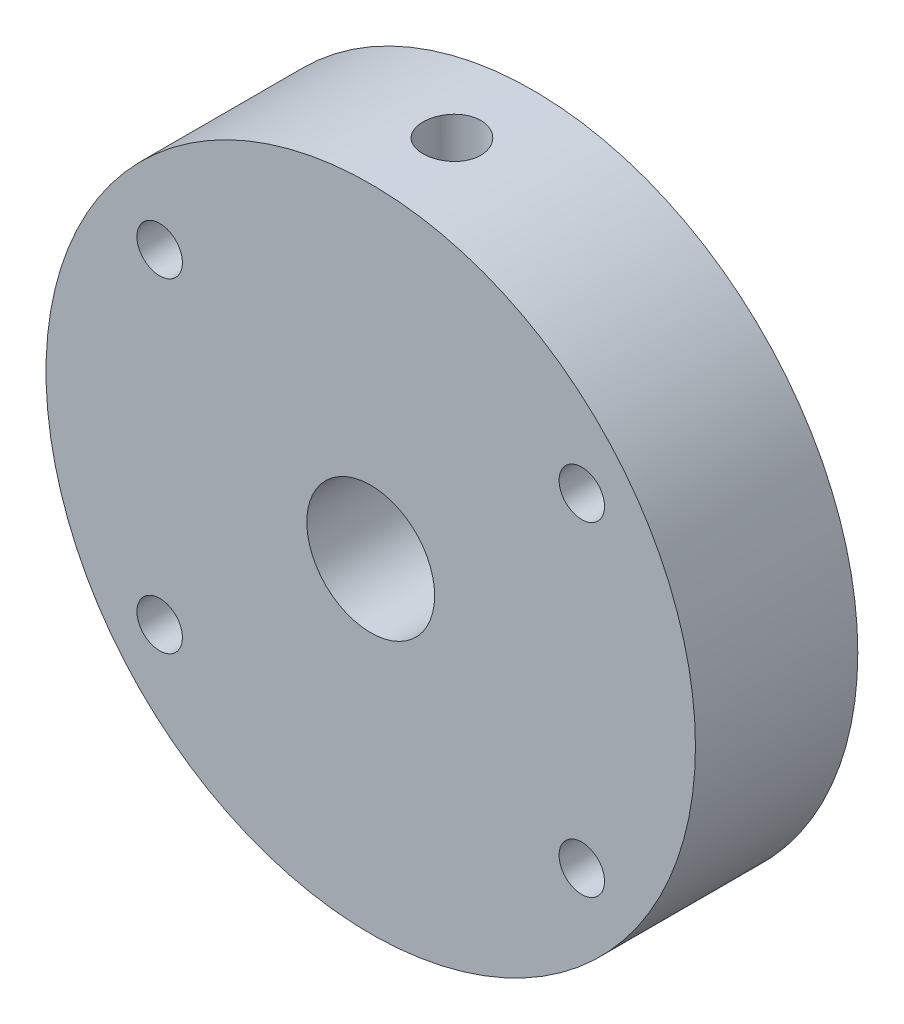
SolidWorks part; units mm, degrees
material "ABS PC"
ref_plane "Front Plane" through (0, 0, 0) normal (0, 0, 1) x (1, 0, 0)
ref_plane "Top Plane" through (0, 0, 0) normal (0, 1, 0) x (1, 0, 0)
ref_plane "Right Plane" through (0, 0, 0) normal (1, 0, 0) x (0, 0, -1)
sketch "Sketch1" plane through (0, 0, 0) normal (0, 0, 1) x (1, 0, 0)
  circle A0 centre (0, 0) radius 12.7
  circle A1 centre (0, 0) radius 2.5
  dimension "D1" = 25.4
  dimension "D2" = 5
extrude "Boss-Extrude1" add sketch "Sketch1" along normal blind 6.35
hole_wizard "#2-56 Tapped Hole1" positions "Sketch4" profile "Sketch3" tap size "#2-56" standard "ANSI Inch" end condition through all
sketch "Sketch4" plane through (0, 0, 6.35) normal (0, 0, 1) x (1, 0, 0)
  line L1 (-8.255, -6.35) -> (8.255, -6.35) construction
  line L2 (-8.255, -6.35) -> (-8.255, 6.35) construction
  line L3 (-8.255, 6.35) -> (8.255, 6.35) construction
  line L4 (8.255, -6.35) -> (8.255, 6.35) construction
  line L5 (-8.255, -6.35) -> (8.255, 6.35) construction
  line L6 (-8.255, 6.35) -> (8.255, -6.35) construction
  circle A0 centre (0, 0) radius 2.5 construction
  point P0 (-8.255, 6.35)
  point P2 (8.255, 6.35)
  point P4 (8.255, -6.35)
  point P6 (-8.255, -6.35)
  dimension "D3" = 5
  dimension "D1" = 12.7
  dimension "D2" = 16.51
sketch "Sketch3" plane through (-8.255, 6.35, 6.35) normal (1, 0, 0) x (0, -1, 0)
  line L0 (0, 0) -> (0, 6.35)
  line L1 (0, 6.35) -> (0.889, 6.35)
  line L2 (0.889, 6.35) -> (0.889, 0)
  line L5 (0.889, 0) -> (0, 0)
  line L11 (0, -6.35) -> (0, 107.95) construction
  dimension "Thru Tap Drill Dia." = 1.778
  dimension "Thru Tap Drill Depth" = 6.35
cosmetic thread "Hole Thread1"
cosmetic thread "Hole Thread2"
cosmetic thread "Hole Thread3"
cosmetic thread "Hole Thread4"
hole_wizard "#4-40 Tapped Hole1" positions "Sketch7" profile "Sketch6" tap size "#4-40" standard "ANSI Inch" end condition through all
sketch "Sketch7" plane through (0, 0, 0) normal (0, 1, 0) x (1, 0, 0)
  line L0 (-12.7, -6.35) -> (12.7, -6.35) construction
  line L1 (-12.7, -6.35) -> (12.7, -6.35) construction
  line L2 (0, -6.35) -> (0, 0) construction
  point P0 (0, -3.175)
sketch "Sketch6" plane through (0, 0, 3.175) normal (1, 0, 0) x (0, 0, -1)
  line L0 (0, 0) -> (0, 12.7)
  line L1 (0, 12.7) -> (1.1303, 12.7)
  line L2 (1.1303, 12.7) -> (1.1303, 0)
  line L5 (1.1303, 0) -> (0, 0)
  line L11 (0, -6.35) -> (0, 107.95) construction
  dimension "Thru Tap Drill Dia." = 2.2606
  dimension "Thru Tap Drill Depth" = 12.7
cosmetic thread "Hole Thread5"
